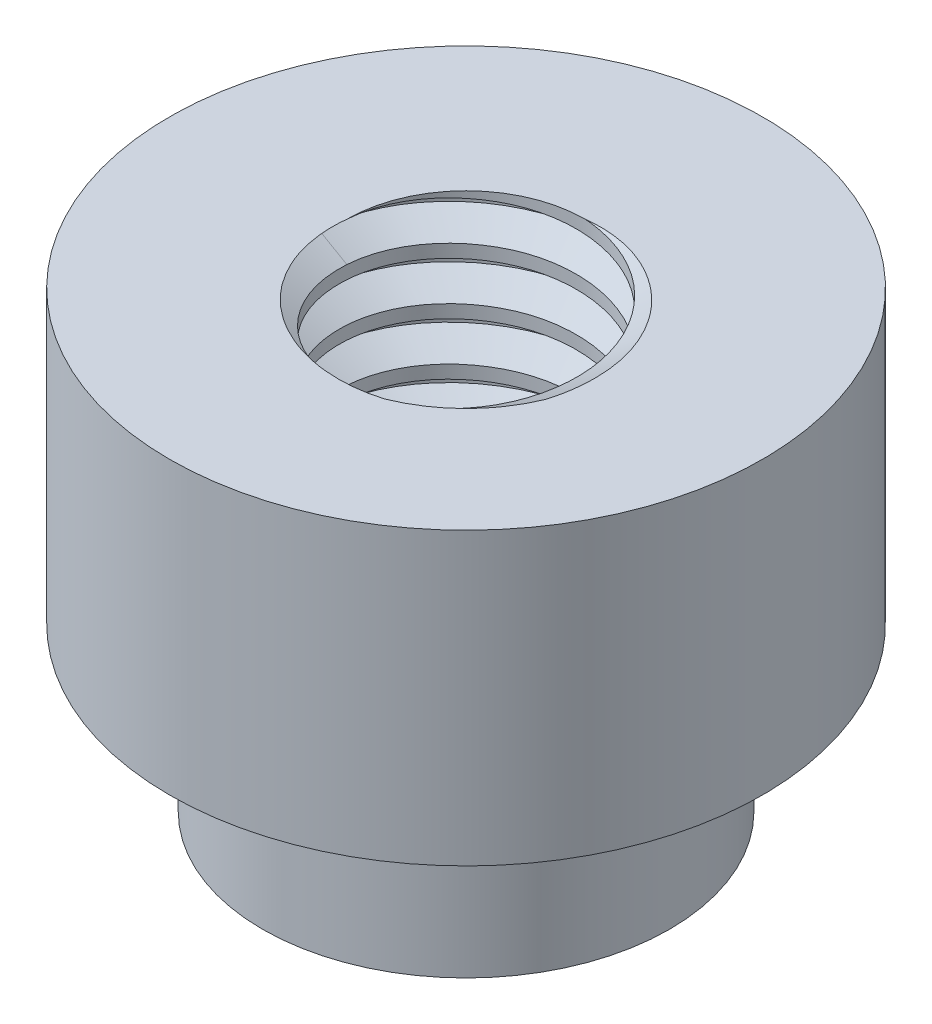
SolidWorks part; units mm, degrees
ref_plane "Front Plane" through (0, 0, 0) normal (0, 0, 1) x (1, 0, 0)
ref_plane "Top Plane" through (0, 0, 0) normal (0, 1, 0) x (1, 0, 0)
ref_plane "Right Plane" through (0, 0, 0) normal (1, 0, 0) x (0, 0, -1)
sketch "Sketch1" plane through (0, 0, 0) normal (0, 1, 0) x (1, 0, 0)
  circle A0 centre (0, 0) radius 1.75
  dimension "D1" = 3.5
extrude "Boss-Extrude1" add sketch "Sketch1" along normal blind 1.4
sketch "Sketch2" plane through (0, 1.4, 0) normal (0, 1, 0) x (1, 0, 0)
  circle A0 centre (0, 0) radius 2.55
  dimension "D1" = 5.1
extrude "Boss-Extrude2" add sketch "Sketch2" along normal blind 2.5
hole_wizard "Tap Drill for M2.5x0.45 Tap1" positions "Sketch4" profile "Sketch5" hole size "M2.5x0.45" standard "ANSI Metric" end condition through all
sketch "Sketch4" plane through (0, 3.9, 0) normal (0, 1, 0) x (1, 0, 0)
  point P0 (0, 0)
sketch "Sketch5" plane through (0, 3.9, 0) normal (1, 0, 0) x (0, 0, 1)
  line L0 (0, 0) -> (0, 3.9)
  line L1 (0, 3.9) -> (1.025, 3.9)
  line L2 (1.025, 3.9) -> (1.025, 0)
  line L5 (1.025, 0) -> (0, 0)
  line L11 (0, -6.35) -> (0, 107.95) construction
  dimension "Thru Hole Dia." = 2.05
  dimension "Thru Hole Depth" = 3.9
thread "Thread1" pitch 0.45 start angle 0, offset 0, length 0, pitch 0.45, diameter 2.05
ref_plane "Plane1" through (-1.025, 3.9, 0) normal (0, 0, 1) x (-1, 0, 0)
sketch "Thread Profile1" plane through (-1.025, 3.9, 0) normal (0, 0, 1) x (-1, 0, 0)
  line L0 (0, 0) -> (0, 0.45) construction
  line L1 (0, 0) -> (0.2436, 0.1406)
  line L2 (0.2436, 0.1406) -> (0.2436, 0.1969)
  line L3 (0.2436, 0.1969) -> (0, 0.3375)
  line L4 (0.2436, 0.1687) -> (0, 0.1687) construction
  line L11 (0, 0) -> (0, 0.3375)
  point P2 (0, 0)
  dimension "Pitch" = 0.45
  dimension "Profile_Angle" = 60
  dimension "Profile_Land" = 0.0562
  dimension "Profile_Height" = 0.2436
thread "Thread2" pitch 0.45 profile "Thread Profile2" start angle 0, offset 0, length 0, pitch 0.45, diameter 2.05
ref_plane "Plane2" through (-1.025, 3.9, 0) normal (0, 0, 1) x (-1, 0, 0)
sketch "Thread Profile2" plane through (-1.025, 3.9, 0) normal (0, 0, 1) x (-1, 0, 0)
  line L0 (0, 0) -> (0, 0.45) construction
  line L1 (0, 0) -> (0.2436, 0.1406)
  line L2 (0.2436, 0.1406) -> (0.2436, 0.1969)
  line L3 (0.2436, 0.1969) -> (0, 0.3375)
  line L4 (0.2436, 0.1687) -> (0, 0.1687) construction
  line L11 (0, 0) -> (0, 0.3375)
  point P2 (0, 0)
  dimension "Pitch" = 0.45
  dimension "Profile_Angle" = 60
  dimension "Profile_Land" = 0.0562
  dimension "Profile_Height" = 0.2436
